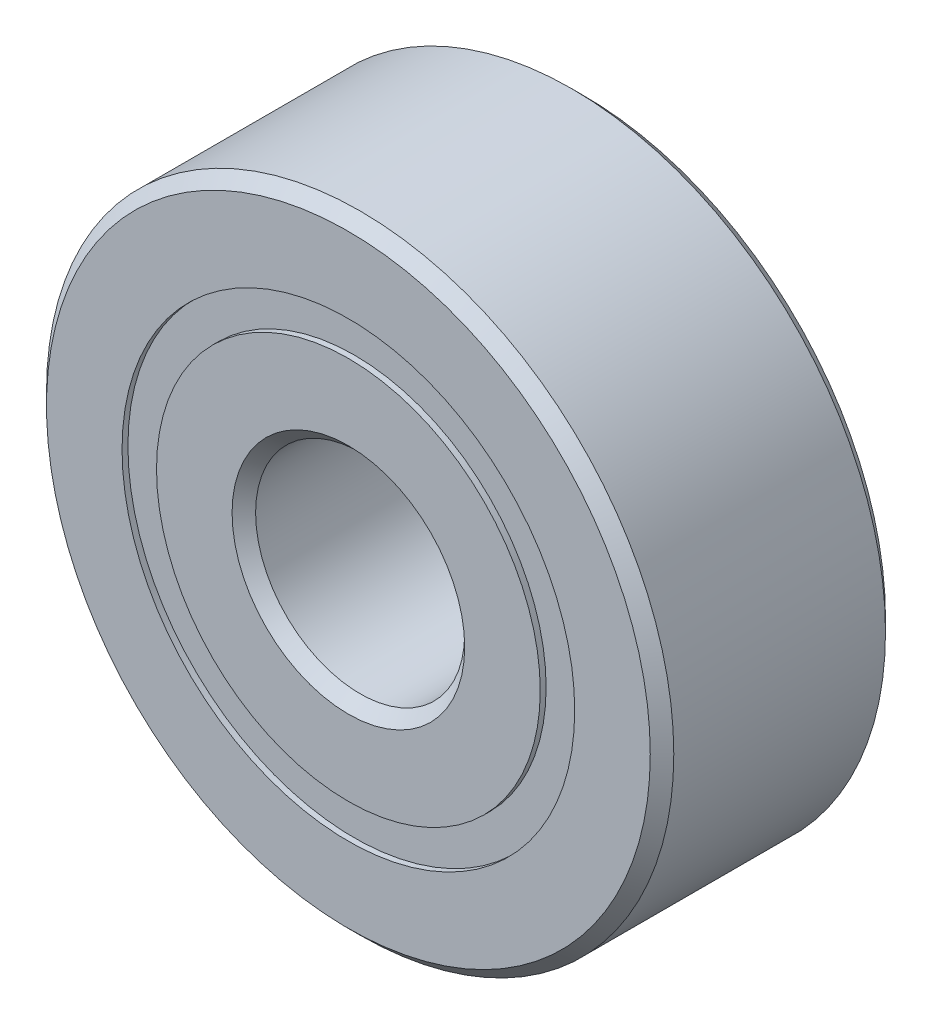
SolidWorks part; units mm, degrees
material "Plain Carbon Steel"
ref_plane "Front Plane" through (0, 0, 0) normal (0, 0, 1) x (1, 0, 0)
ref_plane "Top Plane" through (0, 0, 0) normal (0, 1, 0) x (1, 0, 0)
ref_plane "Right Plane" through (0, 0, 0) normal (1, 0, 0) x (0, 0, -1)
sketch "Sketch1" plane through (0, 0, 0) normal (1, 0, 0) x (0, 0, -1)
  line L0 (-3.5719, 0) -> (3.5719, 0) construction
  line L1 (0, 9.525) -> (0, -9.525) construction
  line L2 (3.2147, 9.525) -> (-3.2147, 9.525)
  line L3 (-3.2147, 9.525) -> (-3.5719, 9.1678)
  line L4 (-3.5719, 9.1678) -> (-3.5719, 6.8734)
  line L5 (-3.5719, 6.8734) -> (-1.5875, 6.8734)
  line L6 (3.5719, 6.8734) -> (1.5875, 6.8734)
  line L7 (3.5719, 9.1678) -> (3.5719, 6.8734)
  line L8 (3.2147, 9.525) -> (3.5719, 9.1678)
  line L9 (0, 9.525) -> (0, 6.35) construction
  line L10 (0, 6.35) -> (0, 3.175) construction
  arc A0 (-1.5875, 6.8734) -> (1.5875, 6.8734) centre (0, 6.35) cw
  point P14 (0, 3.175)
  dimension "Width" = 7.1437
  dimension "OD" = 19.05
  dimension "D1" = 45
  dimension "D2" = 0.3572
  dimension "Shaft Dia" = 6.35
  dimension "D3" = 3.175
  dimension "D4" = 0.5234
revolve "Revolve1" add sketch "Sketch1" angle 360 about L0
sketch "Sketch3" plane through (0, 0, 0) normal (1, 0, 0) x (0, 0, -1)
  line L0 (-3.5719, 5.8266) -> (-1.5875, 5.8266)
  line L1 (0, 9.525) -> (0, -9.525) construction
  line L2 (-3.5719, 9.1678) -> (-3.5719, 6.8734) construction
  line L3 (-3.5719, 5.8266) -> (-3.5719, 3.5322)
  line L4 (-3.2147, 9.525) -> (-3.5719, 9.1678) construction
  line L5 (-3.5719, 3.5322) -> (-3.2147, 3.175)
  line L6 (-3.2147, 3.175) -> (3.2147, 3.175)
  line L7 (3.2147, 9.525) -> (3.2147, -9.525) construction
  line L8 (3.2147, 3.175) -> (3.5719, 3.5322)
  line L9 (3.5719, -9.1678) -> (3.5719, 9.1678) construction
  line L10 (3.5719, 3.5322) -> (3.5719, 5.8266)
  line L11 (3.5719, 5.8266) -> (1.5875, 5.8266)
  line L13 (3.2147, 9.525) -> (3.5719, 9.1678) construction
  arc A0 (1.5875, 6.8734) -> (-1.5875, 6.8734) centre (0, 6.35) ccw construction
  arc A1 (1.5875, 5.8266) -> (-1.5875, 5.8266) centre (0, 6.35) cw
revolve "Revolve3" add sketch "Sketch3" angle 360 about L0
sketch "Sketch4" plane through (0, 0, 0) normal (1, 0, 0) x (0, 0, -1)
  line L0 (-1.6715, 6.35) -> (1.6715, 6.35)
  arc A2 (-1.6715, 6.35) -> (1.6715, 6.35) centre (0, 6.35) cw
  arc A3 (1.5875, 6.8734) -> (-1.5875, 6.8734) centre (0, 6.35) ccw construction
revolve "Revolve4" add sketch "Sketch4" angle 360 about L0
ref_axis "Axis1" through (0, 0, -3.5719) along (0, 0, 1)
pattern_circular "CirPattern1" count 8 over 360 about axis through (0, 0, -3.5719) along (0, 0, 1) of bodies 104
sketch "Sketch5" plane through (0, 0, 0) normal (1, 0, 0) x (0, 0, -1)
  line L0 (-3.5719, 6.8734) -> (-1.5875, 6.8734) construction
  line L1 (-3.3933, 6.8734) -> (-1.6715, 6.8734)
  line L2 (-3.3933, 6.8734) -> (-3.3933, 5.8266)
  line L3 (-3.3933, 5.8266) -> (-1.6715, 5.8266)
  line L4 (-1.6715, 6.8734) -> (-1.6715, 5.8266)
  line L5 (-3.5719, 5.8266) -> (-1.5875, 5.8266) construction
  line L6 (3.5719, 6.8734) -> (1.5875, 6.8734) construction
  line L7 (3.3933, 6.8734) -> (1.6715, 6.8734)
  line L8 (3.3933, 6.8734) -> (3.3933, 5.8266)
  line L9 (3.3933, 5.8266) -> (1.6715, 5.8266)
  line L10 (1.6715, 6.8734) -> (1.6715, 5.8266)
  line L11 (3.5719, 5.8266) -> (1.5875, 5.8266) construction
  line L12 (-3.2147, 9.525) -> (-3.5719, 9.1678) construction
  point P18 (-3.3933, 9.3464)
revolve "Revolve5" add sketch "Sketch5" angle 360 about L0
equation "\"D2@Sketch1\" = \"Width@Sketch1\"*.05"
equation "\"D3@Sketch1\" = \"Width@Sketch1\"/2.25"
equation "\"D4@Sketch1\" = (((\"OD@Sketch1\"-\"Width@Sketch1\")/2)/3.25)/3.5"
equation "\"D2@CirPattern1\" = 360/\"Balls@CirPattern1\""
